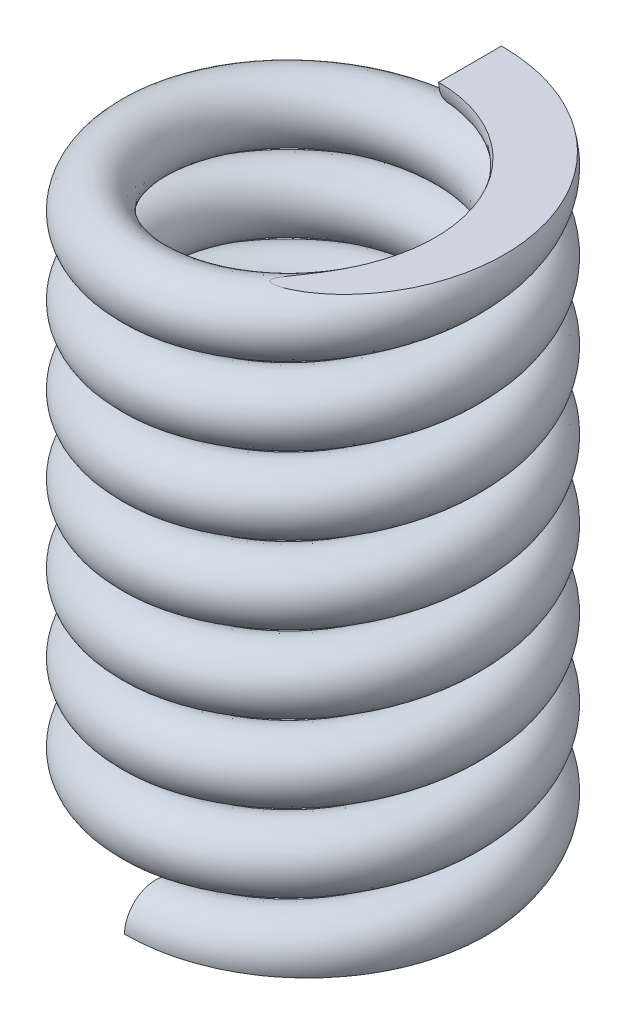
SolidWorks part; units mm, degrees
note: '?' marks a value the reader was unsure of.
material "Алюминиевая бронза"
ref_plane "Спереди" through (0, 0, 0) normal (0, 0, 1) x (1, 0, 0)
ref_plane "Сверху" through (0, 0, 0) normal (0, 1, 0) x (1, 0, 0)
ref_plane "Справа" through (0, 0, 0) normal (1, 0, 0) x (0, 0, -1)
sketch "Эскиз1" plane through (0, 0, 0) normal (0, 1, 0) x (1, 0, 0)
  circle A0 centre (0, 0) radius 7.5
  dimension "D1" = 15
curve "Спираль1" pitch 3.08 height 23.1 turns 7.5
sketch "Эскиз2" plane through (0, 0, 0) normal (1, 0, 0) x (0, 0, -1)
  circle A0 centre (-6.25, 0) radius 1.25
  point P2 (-7.5, 0)
  dimension "D1" = 2.5
sweep "По траектории1" add profiles "Эскиз2" path "Спираль1"
other "Сечение1"
ref_plane "Плоскость1" through (0, 23.1, 0) normal (0, 1, 0) x (1, 0, 0)
other "Сечение2" flip cut yes
sketch "Эскиз3" plane through (0, 0, 0) normal (0, 0, 1) x (1, 0, 0)
  line L0 (0, 0) -> (0, 35.2558)
ref_axis "Ось1" through (0, 0, 0) along (0, 1, 0)?
